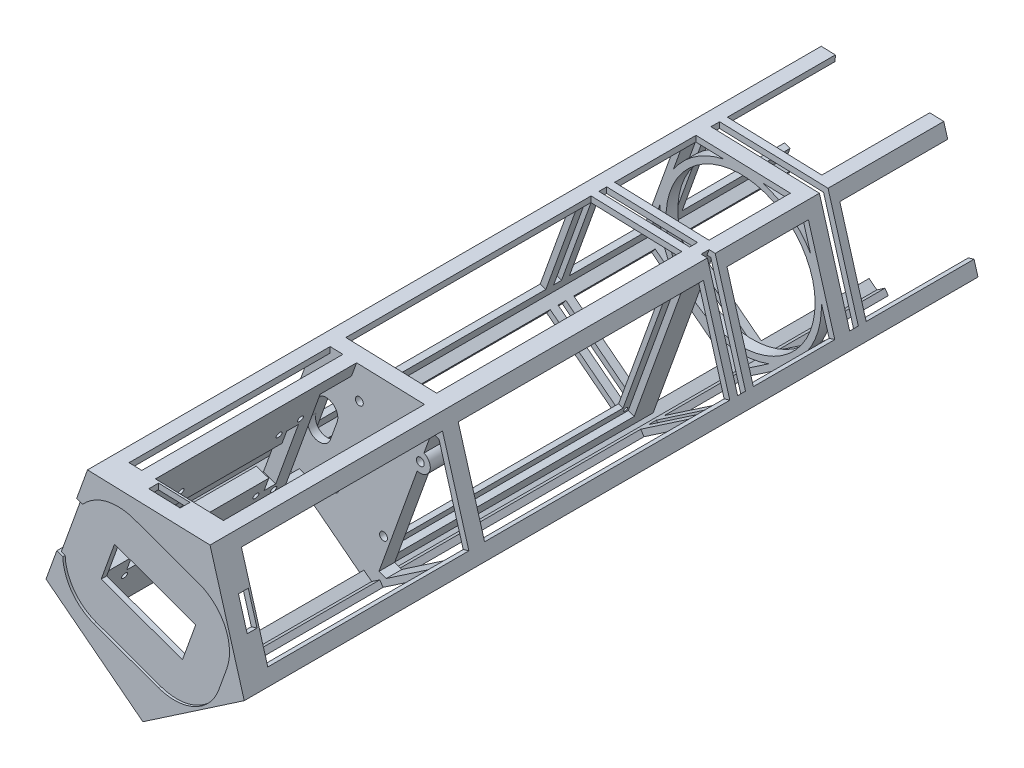
SolidWorks part; units mm, degrees
ref_plane "Front Plane" through (0, 0, 0) normal (0, 0, 1) x (1, 0, 0)
ref_plane "Top Plane" through (0, 0, 0) normal (0, 1, 0) x (1, 0, 0)
ref_plane "Right Plane" through (0, 0, 0) normal (1, 0, 0) x (0, 0, -1)
sketch "Sketch3" plane through (0, 0, 0) normal (0, 0, 1) x (1, 0, 0)
  line L0 (0, 0) -> (16.2851, 21.0012) construction
  line L1 (15.1489, 19.536) -> (-13.8986, 20.4445)
  line L2 (-13.8986, 20.4445) -> (-23.7387, -6.9006)
  line L3 (-23.7387, -6.9006) -> (-0.7728, -24.7093)
  line L4 (-0.7728, -24.7093) -> (23.2611, -8.3705)
  line L5 (0, 0) -> (29.9163, 0) construction
  line L6 (0, 0) -> (25.0057, -8.9983) construction
  line L10 (-0.8307, -26.5625) -> (25.0057, -8.9983)
  line L11 (25.0057, -8.9983) -> (16.2851, 21.0012)
  line L12 (16.2851, 21.0012) -> (-14.941, 21.9778)
  line L13 (-14.941, 21.9778) -> (-25.5191, -7.4182)
  line L14 (-25.5191, -7.4182) -> (-0.8307, -26.5625)
  line L15 (23.2611, -8.3705) -> (15.1489, 19.536)
  circle A0 centre (0, 0) radius 20 construction
  dimension "D2" = 40
extrude "Boss-Extrude2" add sketch "Sketch3" along normal blind 185
ref_plane "Plane1" through (0, 0, 92.5) normal (0, 0, 1) x (1, 0, 0)
sketch "Sketch4" plane through (0, 0, 0) normal (0, 0, -1) x (-1, 0, 0)
  line L0 (14.745, 18.0921) -> (16.1564, 18.6)
  line L1 (13.8986, 20.4445) -> (23.7387, -6.9006) construction
  line L2 (14.941, 21.9778) -> (25.5191, -7.4182) construction
  line L3 (24.3036, -4.0404) -> (22.8922, -4.5483)
  line L4 (22.8922, -4.5483) -> (14.745, 18.0921)
  line L5 (24.3036, -4.0404) -> (16.1564, 18.6)
  dimension "D1" = 2.5
  dimension "D2" = 2.5
extrude "Cut-Extrude1" cut sketch "Sketch4" against normal offset from surface (180 mm away) 5 up to face at (0, 0, 185)
ref_point "Point1"
ref_axis "Axis1" through (0, 0, 185) along (0, 0, 1)
pattern_circular "CirPattern1" count 5 over 360 about axis through (0, 0, 185) along (0, 0, 1) of "Cut-Extrude1"
ref_plane "Plane2" through (0, 0, 92.5) normal (0, 0, 1) x (1, 0, 0)
sketch "Sketch5" plane through (0, 0, 92.5) normal (0, 0, 1) x (1, 0, 0)
  line L0 (-2.0696, -25.6018) -> (14.7182, 21.0502) construction
  line L2 (-24.1133, -8.5083) -> (-1.8275, -25.7895) construction
  line L3 (23.2611, -8.3705) -> (0, 0) construction
  line L4 (-4.3961, -23.7977) -> (11.7756, 21.1422)
  line L8 (-2.0696, -25.6018) -> (-4.3961, -23.7977)
  line L10 (14.7182, 21.0502) -> (11.7756, 21.1422)
  line L11 (-2.0696, -25.6018) -> (14.7182, 21.0502)
  line L12 (-22.8004, 22.2236) -> (6.2471, 21.3151) construction
  dimension "D1" = 18
  dimension "D2" = 2.8
extrude "Boss-Extrude3" add sketch "Sketch5" along normal mid plane 64.5
sketch "Sketch6" plane through (0, 0, 124.75) normal (0, 0, 1) x (1, 0, 0)
  line L5 (-25.5191, -7.4182) -> (-0.8307, -26.5625)
  line L6 (-0.8307, -26.5625) -> (25.0057, -8.9983)
  line L7 (25.0057, -8.9983) -> (16.2851, 21.0012)
  line L8 (16.2851, 21.0012) -> (-14.941, 21.9778)
  line L9 (-14.941, 21.9778) -> (-25.5191, -7.4182)
  line L10 (-25.5191, -7.4182) -> (-0.8307, -26.5625)
  line L11 (-0.8307, -26.5625) -> (25.0057, -8.9983)
  line L12 (25.0057, -8.9983) -> (16.2851, 21.0012)
  line L13 (16.2851, 21.0012) -> (-14.941, 21.9778)
  line L14 (-14.941, 21.9778) -> (-25.5191, -7.4182)
  dimension "D1" = 0
extrude "Boss-Extrude4" add sketch "Sketch6" along normal blind 4
sketch "Sketch7" plane through (0, 0, 124.75) normal (0, 0, -1) x (-1, 0, 0)
  line L0 (-3.6897, -1.3278) -> (20.23, 7.2798) construction
  line L1 (-11.7756, 21.1422) -> (4.3961, -23.7977) construction
  line L2 (16.1564, 18.6) -> (24.3036, -4.0404) construction
  line L4 (19.0326, -2.4504) -> (13.1071, 14.0159)
  line L5 (0.2139, -9.2223) -> (-5.7115, 7.244)
  line L7 (19.0326, -2.4504) -> (-5.7115, 7.244) construction
  line L8 (0.2139, -9.2223) -> (13.1071, 14.0159) construction
  line L9 (9.6232, -5.8364) -> (3.6978, 10.63) construction
  line L11 (-11.7756, 21.1422) -> (4.3961, -23.7977) construction
  arc A0 (-5.7115, 7.244) -> (13.1071, 14.0159) centre (3.6978, 10.63) cw
  arc A1 (0.2139, -9.2223) -> (19.0326, -2.4504) centre (9.6232, -5.8364) ccw
  point P7 (6.6605, 2.3968)
  point P9 (13.0092, -15.2457)
  point P14 (0.3119, 20.0393)
  dimension "D1" = 37.5
  dimension "D2" = 20
  dimension "D3" = 1
extrude "Cut-Extrude2" cut sketch "Sketch7" against normal blind 2
sketch "Sketch8" plane through (6.3243, -2.2758, 0) normal (0.9409, -0.3386, 0) x (0, 0, -1)
  line L0 (-60.25, 0) -> (-124.75, 0) construction
  line L1 (-124.75, -23.2131) -> (-124.75, 23.2131) construction
  line L3 (-60.25, -23.2131) -> (-60.25, 23.2131) construction
  line L5 (-123, -20.5) -> (-123, 20.5)
  line L6 (-123, -20.5) -> (-62, -20.5)
  line L7 (-123, 20.5) -> (-62, 20.5)
  line L8 (-62, -20.5) -> (-62, 20.5)
  line L14 (-62, 20.5) -> (-123, -20.5) construction
  line L15 (-62, -20.5) -> (-123, 20.5) construction
  point P11 (-92.5, 0)
  point P14 (-92.5, 0)
  dimension "D1" = 61
  dimension "D2" = 41
extrude "Cut-Extrude3" cut sketch "Sketch8" against normal blind 1.6
sketch "Sketch9" plane through (4.8189, -1.7341, 0) normal (0.9409, -0.3386, 0) x (0, 0, -1)
  line L8 (-121, -18.5) -> (-64, -18.5)
  line L9 (-64, -18.5) -> (-64, 18.5)
  line L10 (-64, 18.5) -> (-121, 18.5)
  line L11 (-121, 18.5) -> (-121, -18.5)
  line L12 (-121, -18.5) -> (-64, -18.5)
  line L13 (-64, -18.5) -> (-64, 18.5)
  line L14 (-64, 18.5) -> (-121, 18.5)
  line L15 (-121, 18.5) -> (-121, -18.5)
  dimension "D1" = 2
extrude "Cut-Extrude4" cut sketch "Sketch9" against normal up to surface (1.2 mm away) up to face at (3.6897, -1.3278, 92.5)
sketch "Sketch10" plane through (0, 0, 60.25) normal (0, 0, -1) x (-1, 0, 0)
  line L25 (-23.2611, -8.3705) -> (0.7728, -24.7093)
  line L26 (0.7728, -24.7093) -> (23.7387, -6.9006)
  line L27 (23.7387, -6.9006) -> (13.8986, 20.4445)
  line L28 (13.8986, 20.4445) -> (-15.1489, 19.536)
  line L29 (-15.1489, 19.536) -> (-23.2611, -8.3705)
  line L30 (0.8307, -26.5625) -> (25.5191, -7.4182)
  line L31 (-25.0057, -8.9983) -> (0.8307, -26.5625)
  line L32 (-16.2851, 21.0012) -> (-25.0057, -8.9983)
  line L33 (14.941, 21.9778) -> (-16.2851, 21.0012)
  line L34 (25.5191, -7.4182) -> (14.941, 21.9778)
  line L40 (0.8307, -26.5625) -> (25.5191, -7.4182)
  line L41 (-25.0057, -8.9983) -> (0.8307, -26.5625)
  line L42 (-16.2851, 21.0012) -> (-25.0057, -8.9983)
  line L43 (14.941, 21.9778) -> (-16.2851, 21.0012)
  line L44 (25.5191, -7.4182) -> (14.941, 21.9778)
  dimension "D1" = 0
extrude "Boss-Extrude5" add sketch "Sketch10" against normal blind 2
sketch "Sketch11" plane through (0, 0, 60.25) normal (0, 0, -1) x (-1, 0, 0)
  line L0 (3.8621, -22.3137) -> (4.3961, -23.7977)
  line L1 (4.3961, -23.7977) -> (3.6676, -24.3627)
  line L2 (-11.2416, 19.6582) -> (-11.7756, 21.1422)
  line L3 (-11.7756, 21.1422) -> (-12.697, 21.1134)
  line L4 (21.7631, -8.4326) -> (3.8621, -22.3137)
  line L7 (3.8621, -22.3137) -> (-11.2416, 19.6582)
  line L9 (-14.1842, 19.5662) -> (1.5355, -24.1178)
  line L10 (-14.1842, 19.5662) -> (1.5355, -24.1178)
  line L11 (-12.697, 21.1134) -> (11.3529, 21.8656) construction
  line L13 (3.8621, -22.3137) -> (-11.2416, 19.6582) construction
  line L18 (22.6823, -9.618) -> (3.6676, -24.3627) construction
  line L19 (3.8621, -22.3137) -> (-11.2416, 19.6582)
  line L27 (-11.2416, 19.6582) -> (11.3998, 20.3663)
  line L31 (1.5355, -24.1178) -> (2.7484, -23.1773)
  line L33 (1.5355, -24.1178) -> (2.7484, -23.1773)
  line L35 (2.7484, -23.1773) -> (3.6676, -24.3627)
  line L37 (2.7484, -23.1773) -> (3.6676, -24.3627)
  line L39 (3.6676, -24.3627) -> (22.6823, -9.618)
  line L41 (22.6823, -9.618) -> (21.7631, -8.4326)
  line L43 (11.3998, 20.3663) -> (11.3529, 21.8656)
  line L45 (11.3529, 21.8656) -> (-12.697, 21.1134)
  line L47 (-12.697, 21.1134) -> (-12.6502, 19.6141)
  line L48 (-12.697, 21.1134) -> (-12.6502, 19.6141)
  line L49 (-12.6502, 19.6141) -> (-14.1842, 19.5662)
  line L50 (-12.6502, 19.6141) -> (-14.1842, 19.5662)
  dimension "D1" = 0
extrude "Boss-Extrude6" add sketch "Sketch11" along normal blind 4
sketch "Sketch12" plane through (0, 0, 56.25) normal (0, 0, -1) x (-1, 0, 0)
  line L0 (0.7728, -24.7093) -> (23.7387, -6.9006)
  line L1 (23.7387, -6.9006) -> (13.8986, 20.4445)
  line L2 (13.8986, 20.4445) -> (-15.1489, 19.536)
  line L3 (-15.1489, 19.536) -> (-23.2611, -8.3705)
  line L4 (-23.2611, -8.3705) -> (0.7728, -24.7093)
  line L5 (0.8307, -26.5625) -> (25.5191, -7.4182)
  line L6 (-25.0057, -8.9983) -> (0.8307, -26.5625)
  line L7 (-16.2851, 21.0012) -> (-25.0057, -8.9983)
  line L8 (14.941, 21.9778) -> (-16.2851, 21.0012)
  line L9 (25.5191, -7.4182) -> (14.941, 21.9778)
  line L10 (0.8307, -26.5625) -> (25.5191, -7.4182)
  line L11 (-25.0057, -8.9983) -> (0.8307, -26.5625)
  line L12 (-16.2851, 21.0012) -> (-25.0057, -8.9983)
  line L13 (14.941, 21.9778) -> (-16.2851, 21.0012)
  line L14 (25.5191, -7.4182) -> (14.941, 21.9778)
  dimension "D1" = 0
extrude "Boss-Extrude7" add sketch "Sketch12" against normal blind 2
ref_plane "Plane3" through (0, 0, 32.5) normal (0, 0, 1) x (1, 0, 0)
sketch "Sketch14" plane through (0, 0, 32.5) normal (0, 0, 1) x (1, 0, 0)
  line L5 (-25.5191, -7.4182) -> (-0.8307, -26.5625)
  line L6 (-0.8307, -26.5625) -> (25.0057, -8.9983)
  line L7 (25.0057, -8.9983) -> (16.2851, 21.0012)
  line L8 (16.2851, 21.0012) -> (-14.941, 21.9778)
  line L9 (-14.941, 21.9778) -> (-25.5191, -7.4182)
  line L11 (-0.8307, -26.5625) -> (25.0057, -8.9983)
  line L12 (25.0057, -8.9983) -> (16.2851, 21.0012)
  line L16 (23.2611, -8.3705) -> (15.3259, -13.7651)
  line L18 (-0.7728, -24.7093) -> (-8.3554, -18.8294)
  line L20 (-23.7387, -6.9006) -> (-20.4898, 2.1279)
  line L22 (-13.8986, 20.4445) -> (-4.308, 20.1445)
  line L24 (15.1489, 19.536) -> (17.8273, 10.3221)
  line L25 (7.1625, -19.3147) -> (-0.7728, -24.7093)
  line L26 (20.5827, 0.8433) -> (23.2611, -8.3705)
  line L27 (5.5584, 19.8359) -> (15.1489, 19.536)
  line L28 (-17.1475, 11.416) -> (-13.8986, 20.4445)
  line L29 (-16.1561, -12.7805) -> (-23.7387, -6.9006)
  line L30 (16.2851, 21.0012) -> (-14.941, 21.9778)
  line L31 (-14.941, 21.9778) -> (-25.5191, -7.4182)
  line L32 (-25.5191, -7.4182) -> (-0.8307, -26.5625)
  circle A3 centre (0, 0) radius 19
  arc A8 (15.3259, -13.7651) -> (20.5827, 0.8433) centre (0, 0) ccw
  circle A9 centre (0, 0) radius 20.6 construction
  arc A10 (17.8273, 10.3221) -> (5.5584, 19.8359) centre (0, 0) ccw
  arc A11 (-4.308, 20.1445) -> (-17.1475, 11.416) centre (0, 0) ccw
  arc A12 (-20.4898, 2.1279) -> (-16.1561, -12.7805) centre (0, 0) ccw
  arc A13 (-8.3554, -18.8294) -> (7.1625, -19.3147) centre (0, 0) ccw
  dimension "D2" = 38
  dimension "D1" = 0
  dimension "D3" = 1.6
extrude "Boss-Extrude8" add sketch "Sketch14" along normal blind 3
ref_plane "Plane4" through (0, 0, 29.5) normal (0, 0, -1) x (-1, 0, 0)
sketch "Sketch15" plane through (0, 0, 29.5) normal (0, 0, -1) x (-1, 0, 0)
  line L0 (-23.2611, -8.3705) -> (0.7728, -24.7093)
  line L1 (0.7728, -24.7093) -> (23.7387, -6.9006)
  line L2 (23.7387, -6.9006) -> (13.8986, 20.4445)
  line L3 (13.8986, 20.4445) -> (-15.1489, 19.536)
  line L4 (-15.1489, 19.536) -> (-23.2611, -8.3705)
  line L5 (0.8307, -26.5625) -> (25.5191, -7.4182)
  line L6 (-25.0057, -8.9983) -> (0.8307, -26.5625)
  line L7 (-16.2851, 21.0012) -> (-25.0057, -8.9983)
  line L8 (14.941, 21.9778) -> (-16.2851, 21.0012)
  line L9 (25.5191, -7.4182) -> (14.941, 21.9778)
  line L10 (0.8307, -26.5625) -> (25.5191, -7.4182)
  line L11 (-25.0057, -8.9983) -> (0.8307, -26.5625)
  line L12 (-16.2851, 21.0012) -> (-25.0057, -8.9983)
  line L13 (14.941, 21.9778) -> (-16.2851, 21.0012)
  line L14 (25.5191, -7.4182) -> (14.941, 21.9778)
  dimension "D1" = 0
extrude "Boss-Extrude9" add sketch "Sketch15" along normal blind 2
sketch "Sketch18" plane through (0, 0, 32.5) normal (0, 0, -1) x (-1, 0, 0)
  line L0 (22.8922, -4.5483) -> (24.3036, -4.0404)
  line L1 (24.3036, -4.0404) -> (16.1564, 18.6)
  line L2 (16.1564, 18.6) -> (14.745, 18.0921)
  line L3 (14.745, 18.0921) -> (22.8922, -4.5483)
  line L4 (11.3998, 20.3663) -> (11.3529, 21.8656)
  line L5 (11.3529, 21.8656) -> (-12.697, 21.1134)
  line L6 (-12.697, 21.1134) -> (-12.6502, 19.6141)
  line L7 (-12.6502, 19.6141) -> (11.3998, 20.3663)
  line L8 (-15.8468, 17.1354) -> (-17.2872, 17.5541)
  line L9 (-17.2872, 17.5541) -> (-24.0037, -5.5512)
  line L10 (-24.0037, -5.5512) -> (-22.5633, -5.9699)
  line L11 (-22.5633, -5.9699) -> (-15.8468, 17.1354)
  line L12 (-21.1936, -9.7761) -> (-22.0369, -11.0166)
  line L13 (-22.0369, -11.0166) -> (-2.138, -24.5443)
  line L14 (-2.138, -24.5443) -> (-1.2947, -23.3038)
  line L15 (-1.2947, -23.3038) -> (-21.1936, -9.7761)
  line L16 (3.6676, -24.3627) -> (22.6823, -9.618)
  line L17 (22.6823, -9.618) -> (21.7631, -8.4326)
  line L18 (21.7631, -8.4326) -> (2.7484, -23.1773)
  line L19 (2.7484, -23.1773) -> (3.6676, -24.3627)
extrude "Boss-Extrude10" add sketch "Sketch18" along normal blind 0.8
sketch "Sketch29" plane through (0, 0, 185) normal (0, 0, 1) x (1, 0, 0)
  line L5 (-25.5191, -7.4182) -> (-0.8307, -26.5625)
  line L6 (-0.8307, -26.5625) -> (25.0057, -8.9983)
  line L7 (25.0057, -8.9983) -> (16.2851, 21.0012)
  line L8 (16.2851, 21.0012) -> (-14.941, 21.9778)
  line L9 (-14.941, 21.9778) -> (-25.5191, -7.4182)
  line L10 (-25.5191, -7.4182) -> (-0.8307, -26.5625)
  line L11 (-0.8307, -26.5625) -> (25.0057, -8.9983)
  line L12 (25.0057, -8.9983) -> (16.2851, 21.0012)
  line L13 (16.2851, 21.0012) -> (-14.941, 21.9778)
  line L14 (-14.941, 21.9778) -> (-25.5191, -7.4182)
  dimension "D1" = 0
extrude "Boss-Extrude13" add sketch "Sketch29" along normal blind 2
sketch "Sketch30" plane through (0, 0, 187) normal (0, 0, 1) x (1, 0, 0)
  line L0 (25.0057, -8.9983) -> (-20.23, 7.2798) construction
  line L1 (-14.941, 21.9778) -> (-25.5191, -7.4182) construction
  line L2 (3.1542, -17.0767) -> (-13.3121, -11.1513)
  line L3 (18.5086, -9.8487) -> (20.5401, -4.2031)
  line L4 (-20.5401, 4.2031) -> (-18.5086, 9.8487)
  line L5 (13.3121, 11.1513) -> (-3.1542, 17.0767)
  line L6 (14.4454, -21.1398) -> (-14.4454, 21.1398) construction
  line L7 (-24.6033, -7.0881) -> (24.6033, 7.0881) construction
  line L8 (19.5243, -7.0259) -> (-19.5243, 7.0259) construction
  arc A0 (18.5086, -9.8487) -> (3.1542, -17.0767) centre (7.2174, -5.7855) cw
  arc A1 (-18.5086, 9.8487) -> (-3.1542, 17.0767) centre (-7.2174, 5.7855) cw
  arc A2 (-13.3121, -11.1513) -> (-20.5401, 4.2031) centre (-9.2489, 0.1399) cw
  arc A3 (20.5401, -4.2031) -> (13.3121, 11.1513) centre (9.2489, -0.1399) ccw
  point P5 (0, 0)
  dimension "D3" = 12
  dimension "D1" = 30
  dimension "D2" = 41.5
extrude "Cut-Extrude8" cut sketch "Sketch30" against normal blind 0.6
sketch "Sketch31" plane through (0, 0, 186.4) normal (0, 0, 1) x (1, 0, 0)
  line L0 (25.0057, -8.9983) -> (0, 0) construction
  line L1 (12.0432, 0.9801) -> (8.6573, -8.4292)
  line L2 (12.0432, 0.9801) -> (-8.6573, 8.4292)
  line L3 (8.6573, -8.4292) -> (-12.0432, -0.9801)
  line L4 (-8.6573, 8.4292) -> (-12.0432, -0.9801)
  line L5 (12.0432, 0.9801) -> (-12.0432, -0.9801) construction
  line L6 (8.6573, -8.4292) -> (-8.6573, 8.4292) construction
  line L7 (-10.3503, 3.7246) -> (10.3503, -3.7246) construction
  dimension "D1" = 22
  dimension "D2" = 10
extrude "Cut-Extrude9" cut sketch "Sketch31" against normal up to surface (1.4 mm away) up to face at (0, 0, 185)
sketch "Sketch32" plane through (0, 0, 187) normal (0, 0, 1) x (1, 0, 0)
  line L0 (0, 0) -> (-36.3954, 13.0969) construction
  line L1 (-22.7695, 0.2228) -> (-21.2398, -0.3276)
  line L3 (-14.941, 21.9778) -> (-25.5191, -7.4182) construction
  line L4 (-17.6906, 14.3368) -> (-16.1609, 13.7863)
  line L5 (-18.5086, 9.8487) -> (-20.5401, 4.2031) construction
  line L6 (-18.5086, 9.8487) -> (-20.5401, 4.2031)
  line L7 (-17.6906, 14.3368) -> (-22.7695, 0.2228)
  arc A0 (-20.5401, 4.2031) -> (-13.3121, -11.1513) centre (-9.2489, 0.1399) ccw construction
  arc A1 (-20.5401, 4.2031) -> (-13.3121, -11.1513) centre (-9.2489, 0.1399) ccw construction
  arc A3 (-3.1542, 17.0767) -> (-18.5086, 9.8487) centre (-7.2174, 5.7855) ccw construction
  arc A4 (-16.1609, 13.7863) -> (-18.5086, 9.8487) centre (-7.2174, 5.7855) ccw
  arc A5 (-20.5401, 4.2031) -> (-21.2398, -0.3276) centre (-9.2489, 0.1399) ccw
  dimension "D1" = 7.5
extrude "Cut-Extrude11" cut sketch "Sketch32" against normal up to surface (0.6 mm away) up to face at (0, 0, 186.4)
sketch "Sketch34" plane through (0, 0, 186.4) normal (0, 0, 1) x (1, 0, 0)
  line L0 (-22.7695, 0.2228) -> (-17.6906, 14.3368)
  line L1 (-22.7695, 0.2228) -> (-22.0638, -0.0311)
  line L2 (-17.6906, 14.3368) -> (-16.9849, 14.0828)
  line L3 (-22.0638, -0.0311) -> (-16.9849, 14.0828)
  line L4 (-13.3121, -11.1513) -> (3.1542, -17.0767)
  line L5 (18.5086, -9.8487) -> (20.5401, -4.2031)
  line L6 (13.3121, 11.1513) -> (-3.1542, 17.0767)
  line L7 (-18.5086, 9.8487) -> (-20.5401, 4.2031)
  line L8 (-13.3121, -11.1513) -> (3.1542, -17.0767) construction
  line L9 (18.5086, -9.8487) -> (20.5401, -4.2031) construction
  line L10 (13.3121, 11.1513) -> (-3.1542, 17.0767) construction
  line L11 (-18.5086, 9.8487) -> (-20.5401, 4.2031) construction
  arc A4 (3.1542, -17.0767) -> (18.5086, -9.8487) centre (7.2174, -5.7855) ccw
  arc A5 (20.5401, -4.2031) -> (13.3121, 11.1513) centre (9.2489, -0.1399) ccw
  arc A6 (-3.1542, 17.0767) -> (-18.5086, 9.8487) centre (-7.2174, 5.7855) ccw
  arc A7 (-20.5401, 4.2031) -> (-13.3121, -11.1513) centre (-9.2489, 0.1399) ccw
  arc A8 (3.1542, -17.0767) -> (18.5086, -9.8487) centre (7.2174, -5.7855) ccw construction
  arc A9 (20.5401, -4.2031) -> (13.3121, 11.1513) centre (9.2489, -0.1399) ccw construction
  arc A10 (-3.1542, 17.0767) -> (-18.5086, 9.8487) centre (-7.2174, 5.7855) ccw construction
  arc A11 (-20.5401, 4.2031) -> (-13.3121, -11.1513) centre (-9.2489, 0.1399) ccw construction
  dimension "D1" = 0
sketch "Sketch38" plane through (0, 0, 124.75) normal (0, 0, -1) x (-1, 0, 0)
  line L5 (13.8986, 20.4445) -> (-15.1489, 19.536)
  line L6 (-15.1489, 19.536) -> (-23.2611, -8.3705)
  line L7 (-23.2611, -8.3705) -> (0.7728, -24.7093)
  line L8 (0.7728, -24.7093) -> (23.7387, -6.9006)
  line L9 (23.7387, -6.9006) -> (13.8986, 20.4445)
  line L11 (-16.3988, 15.2363) -> (-23.2611, -8.3705)
  line L12 (-23.2611, -8.3705) -> (-2.9303, -22.1919)
  line L16 (-1.0956, -21.5316) -> (-2.9303, -22.1919)
  line L17 (0.03, -24.6596) -> (-15.6897, 19.0244)
  line L18 (-1.0956, -21.5316) -> (-14.5641, 15.8965)
  line L19 (-14.5641, 15.8965) -> (-16.3988, 15.2363)
  dimension "D3" = 1.6
  dimension "D4" = 1.6
  dimension "D1" = 0
  dimension "D2" = 1.6
extrude "Cut-Extrude14" cut sketch "Sketch38" against normal up to surface (4 mm away) up to face at (0, 0, 128.75)
sketch "Sketch40" plane through (-18.8186, 6.7719, 0) normal (0.9409, -0.3386, 0) x (0, 0, -1)
  line L0 (-185, 14.5309) -> (-185, -14.5309) construction
  line L1 (-185, 7.5) -> (-183.5, 7.5)
  line L2 (-185, 7.5) -> (-185, -7.5)
  line L3 (-185, -7.5) -> (-183.5, -7.5)
  line L4 (-183.5, 7.5) -> (-183.5, -7.5)
  line L5 (-183.5, 0) -> (-185, 0) construction
  point P9 (-185, 0)
  dimension "D1" = 15
  dimension "D2" = 1.5
extrude "Cut-Extrude15" cut sketch "Sketch40" against normal up to surface (1.5 mm away) up to face at (-20.23, 7.2798, 30.6)
sketch "Sketch41" plane through (-20.23, 7.2798, 0) normal (-0.9409, 0.3386, 0) x (0, 0, 1)
  line L0 (185, -7.5) -> (186.4, -7.5)
  line L1 (185, 7.5) -> (186.4, 7.5)
  line L2 (185, -7.5) -> (185, 7.5)
  line L3 (186.4, 7.5) -> (186.4, -7.5)
extrude "Cut-Extrude16" cut sketch "Sketch41" against normal blind 0.6
ref_plane "Plane5" through (14.5641, 15.8965, 124.75) normal (0.3386, 0.9409, 0) x (0.9409, -0.3386, 0)
sketch "Sketch42" plane through (0, 0, 128.75) normal (0, 0, 1) x (1, 0, 0)
  line L0 (-20.23, 7.2798) -> (0, 0) construction
  line L1 (-16.1564, 18.6) -> (-24.3036, -4.0404) construction
  line L2 (5.4365, -16.774) -> (-14.8782, -9.4637) construction
  line L3 (5.4365, -16.774) -> (14.8782, 9.4637) construction
  line L4 (-14.8782, -9.4637) -> (-5.4365, 16.774) construction
  line L5 (14.8782, 9.4637) -> (-5.4365, 16.774) construction
  line L6 (5.4365, -16.774) -> (-5.4365, 16.774) construction
  line L7 (-14.8782, -9.4637) -> (14.8782, 9.4637) construction
  line L8 (-3.9066, 13.524) -> (11.6282, 7.9338) construction
  line L9 (4.7208, 13.1189) -> (-4.7208, -13.1189) construction
  line L10 (2.2472, -13.2032) -> (-10.1449, -8.7439) construction
  line L11 (-1.5355, -24.1178) -> (14.1842, 19.5662) construction
  line L12 (-1.5355, -24.1178) -> (14.1842, 19.5662)
  line L13 (12.891, 3.9416) -> (6.1392, -14.8212) construction
  line L14 (12.891, 3.9416) -> (10.6328, 4.7542) construction
  line L15 (6.1392, -14.8212) -> (3.881, -14.0086) construction
  line L16 (10.6328, 4.7542) -> (3.881, -14.0086) construction
  circle A0 centre (11.6282, 7.9338) radius 1
  circle A1 centre (-3.9066, 13.524) radius 1
  circle A2 centre (2.2472, -13.2032) radius 1
  circle A3 centre (-10.1449, -8.7439) radius 1
  point P1 (3.8608, 10.7289)
  point P2 (0, 0)
  point P19 (-3.9488, -10.9735)
  dimension "D4" = 2
  dimension "D7" = 2
  dimension "D1" = 21.59
  dimension "D2" = 27.8848
  dimension "D3" = 16.51
  dimension "D5" = 2.54
  dimension "D6" = 13.17
  dimension "D8" = 2.28
  dimension "D9" = 2.4
sketch "Sketch43" plane through (0, 0, 128.75) normal (0, 0, 1) x (1, 0, 0)
  line L1 (10.8306, 5.5214) -> (12.5507, 10.3013)
  line L2 (12.891, 3.9416) -> (10.6328, 4.7542) construction
  line L3 (12.891, 3.9416) -> (10.6328, 4.7542)
  line L4 (1.0956, -21.5316) -> (14.5641, 15.8965) construction
  arc A0 (12.5507, 10.3013) -> (10.8306, 5.5214) centre (11.6282, 7.9338) cw
  point P4 (12.5507, 10.3013)
  line M27 (1.0956, -21.5316) -> (14.5641, 15.8965)
  dimension "D1" = 2.5409
extrude "Boss-Extrude15" add sketch "Sketch43" against normal up to surface (4 mm away) contours A0 M27 region at (12.6767, 7.5565, 128.75) up to face at (11.7736, -4.2367, 124.75)
sketch "Sketch44" plane through (0, 0, 128.75) normal (0, 0, 1) x (1, 0, 0)
  circle A0 centre (-10.1449, -8.7439) radius 1 construction
  circle A1 centre (-3.9066, 13.524) radius 1 construction
  circle A2 centre (-10.1449, -8.7439) radius 1
  circle A3 centre (-3.9066, 13.524) radius 1
extrude "Cut-Extrude18" cut sketch "Sketch42" against normal blind 3.5 contours A0 | A2
extrude "Cut-Extrude19" cut sketch "Sketch44" against normal blind 1.5
sketch "Sketch45" plane through (0, 0, 128.75) normal (0, 0, 1) x (1, 0, 0)
  line L0 (-2.5743, -18.735) -> (9.9537, 16.0795) construction
  line L1 (-2.5743, -18.735) -> (9.9537, 16.0795) construction
  line L2 (13.2655, 17.0133) -> (-0.6169, -21.5649) construction
  line L3 (13.2655, 17.0133) -> (-0.6169, -21.5649) construction
  line L4 (-4.3961, -23.7977) -> (11.7756, 21.1422)
  line L5 (11.7756, 21.1422) -> (14.7182, 21.0502)
  line L6 (14.7182, 21.0502) -> (-2.0696, -25.6018)
  line L7 (-2.0696, -25.6018) -> (-4.3961, -23.7977)
  line L8 (-22.6823, -9.618) -> (-3.6676, -24.3627) construction
  line L11 (12.697, 21.1134) -> (-11.3529, 21.8656) construction
sketch "Sketch46" plane through (0, 0, 128.75) normal (0, 0, 1) x (1, 0, 0)
  line L0 (-8.1098, 21.7641) -> (-20.1403, -11.5891)
  line L1 (-8.1098, 21.7641) -> (-4.6098, 21.6547)
  line L2 (-20.1403, -11.5891) -> (-17.3745, -13.7339)
  line L3 (-4.6098, 21.6547) -> (-17.3745, -13.7339)
  line L4 (-16.1564, 18.6) -> (-24.3036, -4.0404) construction
  line L5 (-1.5355, -24.1178) -> (14.1842, 19.5662) construction
  line L6 (-1.5355, -24.1178) -> (14.1842, 19.5662)
  line L8 (12.697, 21.1134) -> (-11.3529, 21.8656) construction
  line L9 (-22.6823, -9.618) -> (-3.6676, -24.3627) construction
  line M13 (12.697, 21.1134) -> (-11.3529, 21.8656)
  line M23 (-22.6823, -9.618) -> (-3.6676, -24.3627)
  dimension "D1" = 3.5
  dimension "D2" = 3.5
  dimension "D3" = 6.5
extrude "Boss-Extrude17" add sketch "Sketch46" along normal up to surface (56.25 mm away) contours L3 L0 M13 M23 region at (-12.5431, 4.5184, 128.75) up to face at (-8.552, 3.0775, 185)
sketch "Sketch48" plane through (-14.1227, 5.0941, 0) normal (-0.9407, 0.3393, 0) x (0, 0, 1)
  line L0 (128.75, 18.8059) -> (128.75, -18.8143) construction
  line L1 (128.75, -15) -> (136.75, -15)
  line L2 (128.75, -15) -> (128.75, 15)
  line L3 (128.75, 15) -> (136.75, 15)
  line L4 (136.75, -15) -> (136.75, 15)
  line L5 (128.75, -15) -> (136.75, 15) construction
  line L6 (128.75, 15) -> (136.75, -15) construction
  line L7 (-3.5596, 0) -> (269.0596, 0) construction
  point P0 (132.75, 0)
  dimension "D1" = 8
  dimension "D2" = 30
extrude "Cut-Extrude20" cut sketch "Sketch48" against normal up to surface (3.3295 mm away) up to face at (-10.9922, 3.9602, 168.4375)
sketch "Sketch49" plane through (0, 0, 126.75) normal (0, 0, -1) x (-1, 0, 0)
  line L0 (-2.7488, -0.9892) -> (16.0698, 5.7828) construction
  line L1 (-5.7115, 7.244) -> (0.2139, -9.2223) construction
  line L2 (19.0326, -2.4504) -> (13.1071, 14.0159) construction
  line L3 (12.4006, 7.1193) -> (14.0935, 2.4146) construction
  line L4 (15.2234, 8.1351) -> (16.9163, 3.4304)
  line L5 (9.5778, 6.1035) -> (11.2707, 1.3988)
  arc A0 (15.2234, 8.1351) -> (9.5778, 6.1035) centre (12.4006, 7.1193) ccw
  arc A1 (11.2707, 1.3988) -> (16.9163, 3.4304) centre (14.0935, 2.4146) ccw
  point P8 (13.247, 4.767)
  dimension "D1" = 6
  dimension "D2" = 5
extrude "Cut-Extrude21" cut sketch "Sketch49" against normal up to surface (10 mm away) up to face at (-12.5567, 4.5292, 136.75)
sketch "Sketch50" plane through (-14.1227, 5.0941, 0) normal (-0.9407, 0.3393, 0) x (0, 0, 1)
  line L0 (136.75, 0) -> (181.403, 0) construction
  line L1 (138.0765, -12.1) -> (180.0765, -12.1) construction
  line L2 (138.0765, -12.1) -> (138.0765, 12.1) construction
  line L3 (138.0765, 12.1) -> (180.0765, 12.1) construction
  line L4 (180.0765, -12.1) -> (180.0765, 12.1) construction
  line L5 (138.0765, -12.1) -> (180.0765, 12.1) construction
  line L6 (138.0765, 12.1) -> (180.0765, -12.1) construction
  line L7 (136.75, -15) -> (136.75, 15) construction
  line L8 (159.0765, 12.1) -> (159.0765, -12.1) construction
  circle A0 centre (178.0765, -10.1) radius 0.75
  circle A1 centre (178.0765, 10.1) radius 0.75
  circle A2 centre (140.0765, -10.1) radius 0.75
  circle A3 centre (140.0765, 10.1) radius 0.75
  point P0 (159.0765, 0)
  point P5 (178.0765, -10.85)
  point P6 (178.8265, -10.1)
  dimension "D3" = 1.5
  dimension "D4" = 1.25
  dimension "D1" = 24.2
  dimension "D2" = 42
  dimension "D5" = 1.25
extrude "Cut-Extrude22" cut sketch "Sketch50" against normal up to surface (3.3295 mm away) up to face at (-10.9917, 3.9616, 156.5417)
sketch "Sketch51" plane through (-14.1227, 5.0941, 0) normal (-0.9407, 0.3393, 0) x (0, 0, 1)
  line L0 (180, 0) -> (103.153, 0) construction
  line L1 (143.0765, -8.5) -> (140.0765, -8.5)
  line L2 (143.0765, -8.5) -> (143.0765, -4.9557)
  line L3 (143.0765, 8.5) -> (140.0765, 8.5)
  line L4 (140.0765, -8.5) -> (140.0765, 8.5)
  line L5 (143.0765, -8.5) -> (140.0765, 8.5) construction
  line L6 (143.0765, 8.5) -> (140.0765, -8.5) construction
  line L7 (180, -12.047) -> (180, 12.0147) construction
  line L8 (140.0765, 10.1) -> (140.0765, -10.1) construction
  line L9 (178.0765, 10.1) -> (178.0765, 5.0443) construction
  line L10 (140.0765, 10.1) -> (178.0765, -10.1) construction
  line L11 (140.0765, -10.1) -> (178.0765, 10.1) construction
  line L12 (159.0765, 10.1) -> (159.0765, -10.1) construction
  line L13 (175.0765, 8.5) -> (178.0765, 8.5)
  line L14 (178.0765, -8.5) -> (178.0765, -4.9557)
  line L15 (175.0765, -8.5) -> (178.0765, -8.5)
  line L16 (175.0765, -8.5) -> (175.0765, -4.9557)
  line L17 (143.0765, 5.0443) -> (175.0765, 5.0443)
  line L20 (143.0765, -4.9557) -> (175.0765, -4.9557)
  line L21 (143.0765, 5.0443) -> (175.0765, -4.9557) construction
  line L22 (175.0765, 5.0443) -> (143.0765, -4.9557) construction
  line L23 (143.0765, 5.0443) -> (143.0765, 8.5)
  line L24 (175.0765, 5.0443) -> (175.0765, 8.5)
  line L25 (178.0765, 5.0443) -> (185, 5.0443)
  line L26 (185, 5.0443) -> (185, -4.9557)
  line L27 (185, -4.9557) -> (178.0765, -4.9557)
  line L28 (178.0765, -4.9557) -> (178.0765, -10.1) construction
  line L29 (178.0765, 5.0443) -> (178.0765, 8.5)
  line L30 (185, 16.1438) -> (185, -16.1585) construction
  point P0 (141.5765, 0)
  point P21 (159.0765, 0)
  point P26 (159.0765, 0.0443)
  dimension "D1" = 17
  dimension "D2" = 10
  dimension "D3" = 3
  dimension "D4" = 3.5443
extrude "Cut-Extrude23" cut sketch "Sketch51" against normal up to surface (3.3295 mm away) up to face at (-7.3093, 14.1707, 178.0765)
sketch "Sketch52" plane through (-10.9907, 3.9644, 0) normal (0.9407, -0.3393, 0) x (0, 0, -1)
  line L0 (-170.0765, 8.75) -> (-170.0765, -8.75) construction
  line L1 (-140.0765, 0) -> (-178.0765, 0) construction
  line L2 (-140.0765, 8.5) -> (-140.0765, -8.5) construction
  line L3 (-178.0765, -8.5) -> (-178.0765, -4.9557) construction
  line L4 (-145.0765, 8.75) -> (-145.0765, -8.75) construction
  circle A0 centre (-170.0765, 8.75) radius 0.75
  circle A1 centre (-170.0765, -8.75) radius 0.75
  circle A2 centre (-145.0765, 8.75) radius 0.75
  circle A3 centre (-145.0765, -8.75) radius 0.75
  point P10 (-170.0765, 0)
  point P16 (-145.0765, 0)
  dimension "D1" = 1.5
  dimension "D2" = 17.5
  dimension "D3" = 8
  dimension "D4" = 25
extrude "Cut-Extrude24" cut sketch "Sketch52" against normal up to surface (3.3295 mm away) up to face at (-14.1191, 5.104, 161.199)
sketch "Sketch53" plane through (-20.23, 7.2798, 0) normal (-0.9409, 0.3386, 0) x (0, 0, 1)
  line L0 (183, -4) -> (180.5, -4)
  line L1 (183, -4) -> (183, 4)
  line L2 (180.5, -4) -> (180.5, 4)
  line L3 (183, 4) -> (180.5, 4)
  line L4 (183, -4) -> (180.5, 4) construction
  line L5 (180.5, -4) -> (183, 4) construction
  line L7 (183.5, 0) -> (180, 0) construction
  line L8 (183.5, 7.5) -> (183.5, -7.5) construction
  line L9 (180, -12.0309) -> (180, 12.0309) construction
  point P1 (181.75, 0)
  dimension "D1" = 2.5
  dimension "D2" = 8
extrude "Cut-Extrude25" cut sketch "Sketch53" against normal up to surface (1.5 mm away) up to face at (-18.8186, 6.7719, 165.1667)
pattern_circular "CirPattern5" count 5 over 360 about axis through (0, 0, 185) along (0, 0, 1) of "Cut-Extrude25"
sketch "Sketch54" plane through (4.8189, -1.7341, 0) normal (0.9409, -0.3386, 0) x (0, 0, -1)
  line L0 (-62, 20.5) -> (-123, 20.5) construction
  line L1 (-123, 20.5) -> (-123, -20.5) construction
  line L2 (-64, 0) -> (-121, 0) construction
  line L3 (-64, -18.5) -> (-64, 18.5) construction
  line L4 (-121, 18.5) -> (-121, -18.5) construction
  line L5 (-92.5, 18.5) -> (-92.5, -18.5) construction
  line L6 (-64, 18.5) -> (-121, 18.5) construction
  line L7 (-121, -18.5) -> (-64, -18.5) construction
  circle A0 centre (-122, 19.5) radius 0.5
  circle A1 centre (-122, -19.5) radius 0.5
  circle A2 centre (-63, -19.5) radius 0.5
  circle A3 centre (-63, 19.5) radius 0.5
  dimension "D1" = 1
  dimension "D2" = 1
  dimension "D3" = 1
extrude "Cut-Extrude26" cut sketch "Sketch54" against normal up to surface (1.2 mm away) up to face at (3.6897, -1.3278, 92.5)
ref_plane "Plane8" through (15.2997, 42.5167, 0) normal (-0.3386, -0.9409, 0) x (-0.9409, 0.3386, 0)
sketch "Sketch56" plane through (15.2997, 42.5167, 0) normal (-0.3386, -0.9409, 0) x (-0.9409, 0.3386, 0)
  line L0 (-6.7214, -124.75) -> (-6.7214, -56.25) construction
  line L1 (-6.7214, -124.75) -> (-6.7214, -31.7) construction
  line L2 (-24.4654, -60.25) -> (-24.4654, -58.25) construction
  line L3 (-24.4654, -60.25) -> (-24.4654, -58.25)
  line L4 (-24.4654, -58.25) -> (-6.7214, -58.25)
  line L5 (-6.7214, -58.25) -> (-6.7214, -60.25)
  line L6 (-6.7214, -60.25) -> (-24.4654, -60.25)
  line L7 (-24.4654, -31.7) -> (-24.4654, -29.5) construction
  line L8 (-24.4654, -31.7) -> (-24.4654, -29.5)
  line L9 (-24.4654, -29.5) -> (-6.7214, -29.5)
  line L11 (-6.7214, -31.7) -> (-24.4654, -31.7)
  line L12 (-4.7982, -31.7) -> (-4.7982, -29.5) construction
  line L13 (-4.7982, -31.7) -> (-4.7982, -29.5)
  line L14 (-6.7214, -29.5) -> (-4.7982, -29.5)
  line L15 (-6.7214, -31.7) -> (-4.7982, -31.7)
  line L16 (-6.7214, -29.5) -> (-6.7214, 997.25) construction
extrude "Cut-Extrude28" cut sketch "Sketch56" along normal up to vertex (48.09 mm away) up to point (22.0369, -11.0166, 60.25)
